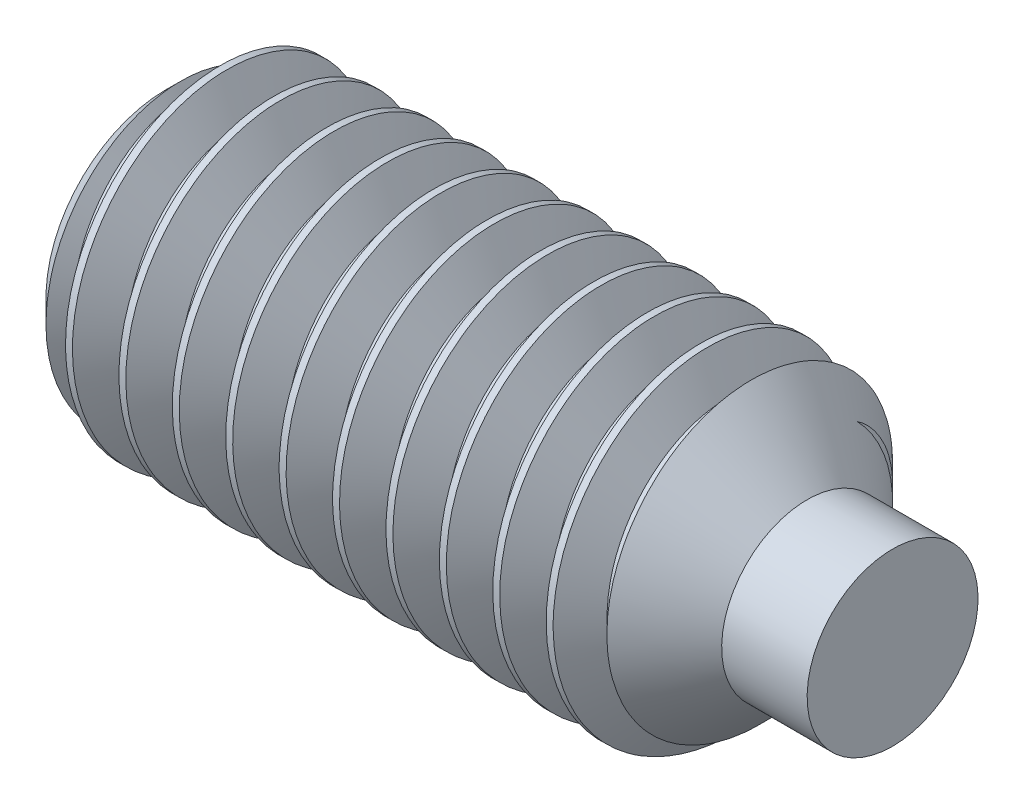
SolidWorks part; units mm, degrees
ref_plane "Front" through (0, 0, 0) normal (0, 0, 1) x (1, 0, 0)
ref_plane "Top" through (0, 0, 0) normal (0, 1, 0) x (1, 0, 0)
ref_plane "Right" through (0, 0, 0) normal (1, 0, 0) x (0, 0, -1)
sketch "Sketch1" plane through (0, 0, 0) normal (0, 0, -1) x (-1, 0, 0)
  line L0 (3.4, 0) -> (-3.4, 0) construction
  line L1 (3.4, 0.75) -> (3.4, -0.75) construction
  line L3 (-3.4, 0.8) -> (-3.4, -0.8) construction
  line L7 (-2.6, 1.5) -> (-2.6, -1.5) construction
  line L8 (-2.6, 1.5) -> (-2.1, 1.5) construction
  point P9 (-3.4, 0)
  point P16 (-2.6, 0)
  point P24 (0, 0)
  dimension "Drive Size" = 1.5
  dimension "Tip Diameter" = 1.6
  dimension "Thread Size" = 3
  dimension "Thread Pitch" = 0.5
  dimension "Length" = 6
  dimension "Tip Length" = 0.8
sketch "Sketch3" plane through (0, 0, 0) normal (0, 0, 1) x (1, 0, 0)
  line L0 (-3.4, 0) -> (3.4, 0) construction
  line L1 (1.8, 0) -> (3.4, 0)
  line L2 (2.6, 1.5) -> (2.6, -1.5) construction
  line L3 (3.4, 0.8) -> (3.4, -0.8) construction
  line L4 (3.4, 0) -> (3.4, 0.8)
  line L5 (3.4, 0.8) -> (1.8, 0.8)
  line L6 (1.8, 0.8) -> (1.8, 0)
  point P0 (2.6, 0)
revolve "Revolve1" add sketch "Sketch3" angle 360 about L0
sketch "Sketch4" plane through (0, 0, 0) normal (0, 0, 1) x (1, 0, 0)
  line L0 (2.6, 0.8) -> (1.9, 1.5)
  line L1 (2.6, 1.5) -> (2.6, -1.5) construction
  line L2 (2.6, 1.5) -> (2.1, 1.5) construction
  line L3 (1.9, 1.5) -> (-3.025, 1.5)
  line L5 (-3.4, 0) -> (1.8, 0)
  line L6 (-3.4, 0) -> (-3.4, 1.125)
  line L7 (-3.4, 1.125) -> (-3.025, 1.5)
  line L8 (3.4, 0.8) -> (1.8, 0.8) construction
  line L9 (1.8, 0.8) -> (1.8, 0) construction
  line L10 (2.6, 0.8) -> (1.8, 0.8)
  line L11 (1.8, 0.8) -> (1.8, 0)
  dimension "D1" = 45
  dimension "D2" = 45
  dimension "D3" = 1.125
revolve "Revolve2" add sketch "Sketch4" angle 360 about L0
sketch "Sketch5" plane through (-3.4, 0, 0) normal (-1, 0, 0) x (0, 0, 1)
  line L1 (0, 0.866) -> (-0.75, 0.433)
  line L2 (-0.75, 0.433) -> (-0.75, -0.433)
  line L3 (-0.75, -0.433) -> (0, -0.866)
  line L4 (0, -0.866) -> (0.75, -0.433)
  line L5 (0.75, -0.433) -> (0.75, 0.433)
  line L6 (0.75, 0.433) -> (0, 0.866)
  circle A0 centre (0, 0) radius 0.75 construction
  dimension "D1" = 1.5
extrude "Cut-Extrude1" cut sketch "Sketch5" against normal blind 0.9375
sketch "Sketch6" plane through (-3.4, 0, 0) normal (-1, 0, 0) x (0, 0, 1)
  circle A0 centre (0, 0) radius 0.866
extrude "Cut-Extrude2" cut sketch "Sketch6" against normal up to next (0.9375 mm away) draft 45
sketch "Sketch9" plane through (0, 0, 0) normal (0, 0, 1) x (1, 0, 0)
  line L1 (-3.4, 0.75) -> (-3.4, -0.75) construction
  point P0 (1.35, -1.5)
  point P1 (3.4, 0.8)
  point P2 (-3.4, 1.5)
  point P3 (3.4, -0.8)
  point P6 (2.6, -1.5)
  point P8 (2.6, 1.5)
  dimension "D1" = 1.25
sketch "Sketch10" plane through (0, 0, 0) normal (1, 0, 0) x (0, 0, -1)
  line L6 (0.75, 0.433) -> (0, 0.866)
  line L7 (0.75, -0.433) -> (0.75, 0.433)
  line L8 (0, -0.866) -> (0.75, -0.433)
  line L9 (-0.75, -0.433) -> (0, -0.866)
  line L10 (-0.75, 0.433) -> (-0.75, -0.433)
  line L11 (0, 0.866) -> (-0.75, 0.433)
  line L12 (0.75, 0.433) -> (0, 0.866)
  line L13 (0.75, -0.433) -> (0.75, 0.433)
  line L14 (0, -0.866) -> (0.75, -0.433)
  line L15 (-0.75, -0.433) -> (0, -0.866)
  line L16 (-0.75, 0.433) -> (-0.75, -0.433)
  line L17 (0, 0.866) -> (-0.75, 0.433)
  circle A0 centre (0, 0) radius 1.5
  dimension "D1" = 0
sketch "Sketch7" plane through (0, 0, 0) normal (0, 0, 1) x (1, 0, 0)
  line L0 (2.5675, 1.5563) -> (2.8175, 1.1233) construction
  line L1 (2.8175, 1.1233) -> (3.0675, 1.5563) construction
  line L2 (3.0675, 1.5563) -> (2.5675, 1.5563) construction
  line L3 (2.6, 1.5) -> (2.1, 1.5) construction
  line L4 (2.8175, 1.5563) -> (2.8175, 1.5) construction
  line L5 (2.8175, 1.1233) -> (2.8175, 1.1796) construction
  line L6 (2.785, 1.1796) -> (2.85, 1.1796)
  line L7 (2.5837, 1.5281) -> (3.0513, 1.5281)
  line L8 (2.6, 1.5) -> (3.035, 1.5) construction
  line L9 (2.5837, 1.5281) -> (2.785, 1.1796)
  line L10 (2.85, 1.1796) -> (3.0513, 1.5281)
  point P11 (2.8175, 1.1796)
  point P14 (2.8175, 1.5281)
  point P16 (2.8175, 1.5)
  dimension "D1" = 0.065
ref_plane "Plane1" through (2.6, 0, 0) normal (1, 0, 0) x (0, 0, -1)
sketch "Sketch8" plane through (2.6, 0, 0) normal (1, 0, 0) x (0, 0, -1)
  circle A0 centre (0, 0) radius 1.5
curve "Helix/Spiral1" pitch 0.5 height 6.5 radius 1.5 centre (2.6, 0, 0) axis (-1, 0, 0) start towards (0, 1, 0)
sweep "Cut-Sweep1" cut profiles "Sketch7" path "Helix/Spiral1"
equation "\"D3@Sketch4\" = \"Thread Size@Sketch1\" * .375"
equation "\"D1@Sketch5\"=\"Drive Size@Sketch1\""
equation "\"D1@Cut-Extrude1\"=\"Drive Size@Sketch1\"*.625"
equation "\"D1@Sketch7\"=\"Thread Pitch@Sketch1\"*.13"
equation "\"D4@Helix/Spiral1\"=\"Thread Pitch@Sketch1\""
equation "\"D1@Sketch9\"=\"Thread Pitch@Sketch1\"*2.5"
equation "\"D3@Helix/Spiral1\"=\"Length@Sketch1\"+\"Thread Pitch@Sketch1\""
